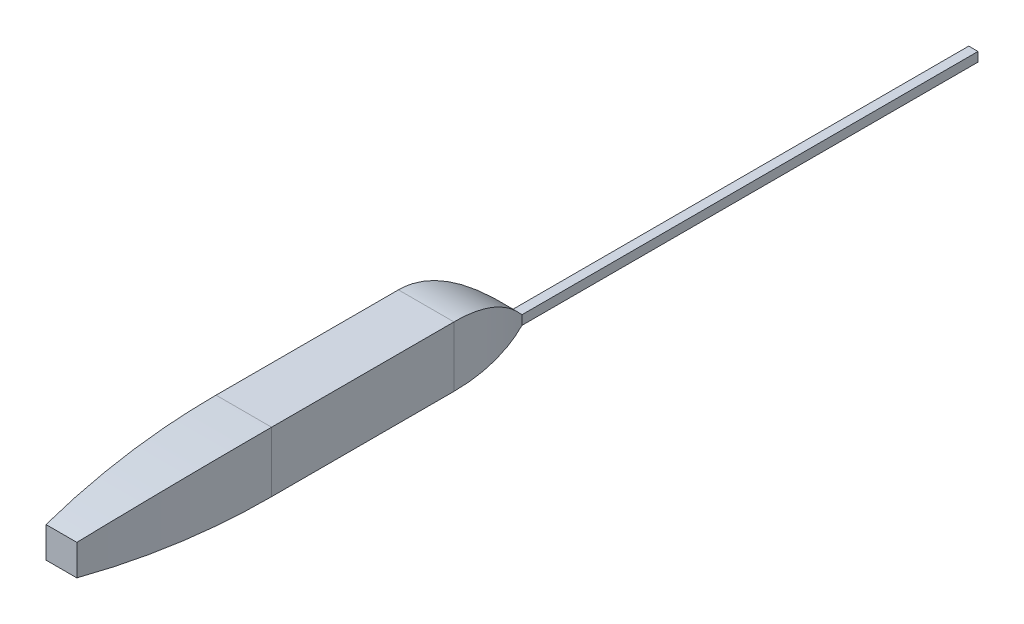
SolidWorks part; units mm, degrees
ref_plane "Front Plane" through (0, 0, 0) normal (0, 0, 1) x (1, 0, 0)
ref_plane "Top Plane" through (0, 0, 0) normal (0, 1, 0) x (1, 0, 0)
ref_plane "Right Plane" through (0, 0, 0) normal (1, 0, 0) x (0, 0, -1)
sketch "Sketch2" plane through (0, 0, 0) normal (0, 0, 1) x (1, 0, 0)
  line L0 (0, 0) -> (14.1421, 14.1421) construction
  line L1 (0, -35.75) -> (0, 35.75) construction
  line L2 (33, 0) -> (-33, 0) construction
  line L3 (-16.6421, 16.6421) -> (16.6421, 16.6421)
  line L4 (-14.1421, -14.1421) -> (14.1421, -14.1421)
  line L5 (-14.1421, -14.1421) -> (-14.1421, 14.1421)
  line L6 (-14.1421, 14.1421) -> (14.1421, 14.1421)
  line L7 (14.1421, -14.1421) -> (14.1421, 14.1421)
  line L8 (-14.1421, -14.1421) -> (14.1421, 14.1421) construction
  line L9 (-14.1421, 14.1421) -> (14.1421, -14.1421) construction
  line L10 (16.6421, -16.6421) -> (16.6421, 16.6421)
  line L11 (-16.6421, -16.6421) -> (16.6421, -16.6421)
  line L12 (-16.6421, -16.6421) -> (-16.6421, 16.6421)
  circle A1 centre (10.253, 10.253) radius 1.5
  circle A2 centre (-10.253, 10.253) radius 1.5
  circle A3 centre (-10.253, -10.253) radius 1.5
  circle A4 centre (10.253, -10.253) radius 1.5
  dimension "D2" = 3
  dimension "D1" = 20
  dimension "D3" = 4
  dimension "D4" = 2.5
sketch "Sketch3" plane through (0, 0, 0) normal (1, 0, 0) x (0, 0, -1)
  line L0 (0, 0) -> (197, 0) construction
  line L1 (197, 32.5) -> (197, -32.5) construction
  line L2 (197, 0) -> (394, 0) construction
  line L3 (0, -16.6421) -> (0, 16.6421) construction
  line L4 (394, -32.5) -> (985, -32.5)
  line L5 (98.5, 0) -> (98.5, 32.5)
  line L6 (0, 16.6421) -> (98.5, 32.5) construction
  line L7 (98.5, 32.5) -> (197, 32.5) construction
  line L8 (394, -32.5) -> (394, 32.5) construction
  line L9 (197, 32.5) -> (394, 32.5)
  line L10 (0, -16.6421) -> (98.5, -32.5) construction
  line L11 (98.5, -32.5) -> (197, -32.5) construction
  line L12 (197, -32.5) -> (394, -32.5)
  line L13 (985, -32.5) -> (985, -22.5)
  line L14 (492.5, -22.5) -> (985, -22.5)
  line L15 (442.25, -22.5) -> (442.25, 32.5) construction
  line L16 (394, 32.5) -> (442.25, 32.5) construction
  line L17 (442.25, 32.5) -> (492.5, -22.5) construction
  line L18 (492.5, -22.5) -> (394, -22.5)
  line L19 (0, -16.6421) -> (0, 16.6421)
  spline S0 degree 2 poles (0, 16.6421) (98.5, 32.5) (197, 32.5) knots 0 0 0 1 1 1
  spline S1 degree 2 poles (0, -16.6421) (98.5, -32.5) (197, -32.5) knots 0 0 0 1 1 1
  spline S2 degree 2 poles (394, 32.5) (442.25, 32.5) (492.5, -22.5) knots 0 0 0 1 1 1
  point P3 (98.5, 0)
  point P6 (197, 0)
  point P7 (442.25, -22.5)
  point P18 (394, 0)
  point P23 (197, 0)
  point P26 (492.5, -22.5)
  point P28 (394, 32.5)
  point P29 (442.25, 32.5)
  point P32 (0, 0)
  point P34 (0, 0)
  dimension "D1" = 65
  dimension "D2" = 197
  dimension "D3" = 197
  dimension "D4" = 591
  dimension "D5" = 10
  dimension "D6" = 98.5
  dimension "D7" = 48.25
sketch "Sketch4" plane through (0, 0, 0) normal (0, 1, 0) x (1, 0, 0)
  line L0 (0, 0) -> (0, 197)
  line L1 (0, 197) -> (0, 394)
  line L2 (0, 394) -> (0, 985)
  line L3 (0, 492.5) -> (0, 985) construction
  line L4 (0, 394) -> (0, 985) construction
  line L5 (-16.6421, 0) -> (16.6421, 0)
  line L6 (-16.6421, 0) -> (16.6421, 0) construction
  line L7 (-30, 98.5) -> (30, 98.5) construction
  line L8 (-30, 197) -> (30, 197) construction
  line L9 (-30, 394) -> (30, 394) construction
  line L10 (-30, 442.25) -> (30, 442.25) construction
  line L11 (-5, 985) -> (5, 985)
  line L12 (30, 197) -> (30, 98.5) construction
  line L13 (30, 98.5) -> (16.6421, 0) construction
  line L14 (30, 197) -> (30, 394)
  line L15 (5, 985) -> (5, 394) construction
  line L16 (-5, 985) -> (-5, 394) construction
  line L17 (30, 394) -> (30, 442.25) construction
  line L18 (30, 442.25) -> (5, 492.5) construction
  line L19 (5, 492.5) -> (5, 985)
  line L20 (-30, 394) -> (-30, 442.25) construction
  line L21 (-30, 442.25) -> (-5, 492.5) construction
  line L22 (-5, 492.5) -> (-5, 985)
  line L23 (-30, 197) -> (-30, 98.5) construction
  line L24 (-30, 98.5) -> (-16.6421, 0) construction
  line L25 (-30, 197) -> (-30, 394)
  spline S0 degree 2 poles (30, 197) (30, 98.5) (16.6421, 0) knots 0 0 0 1 1 1
  spline S1 degree 2 poles (30, 394) (30, 442.25) (5, 492.5) knots 0 0 0 1 1 1
  spline S2 degree 2 poles (-30, 394) (-30, 442.25) (-5, 492.5) knots 0 0 0 1 1 1
  spline S3 degree 2 poles (-30, 197) (-30, 98.5) (-16.6421, 0) knots 0 0 0 1 1 1
  point P4 (5, 492.5)
  point P16 (0, 0)
  point P20 (0, 98.5)
  point P23 (0, 197)
  point P25 (0, 394)
  point P29 (0, 442.25)
  point P32 (0, 985)
  point P34 (0, 492.5)
  dimension "D1" = 60
  dimension "D2" = 60
  dimension "D3" = 60
  dimension "D4" = 10
  dimension "D5" = 98.5
  dimension "D6" = 591
extrude "Boss-Extrude1" add sketch "Sketch4" along normal blind 50 and the other way blind 50 contours S2 L22 L11 L19 S1 L14 S0 L5 S3 L25
extrude "Cut-Extrude1" cut sketch "Sketch3" against normal blind 50 and the other way blind 50 flip side to cut contours S2 L9 S0 L19 S1 L12 L4 L13 L14
